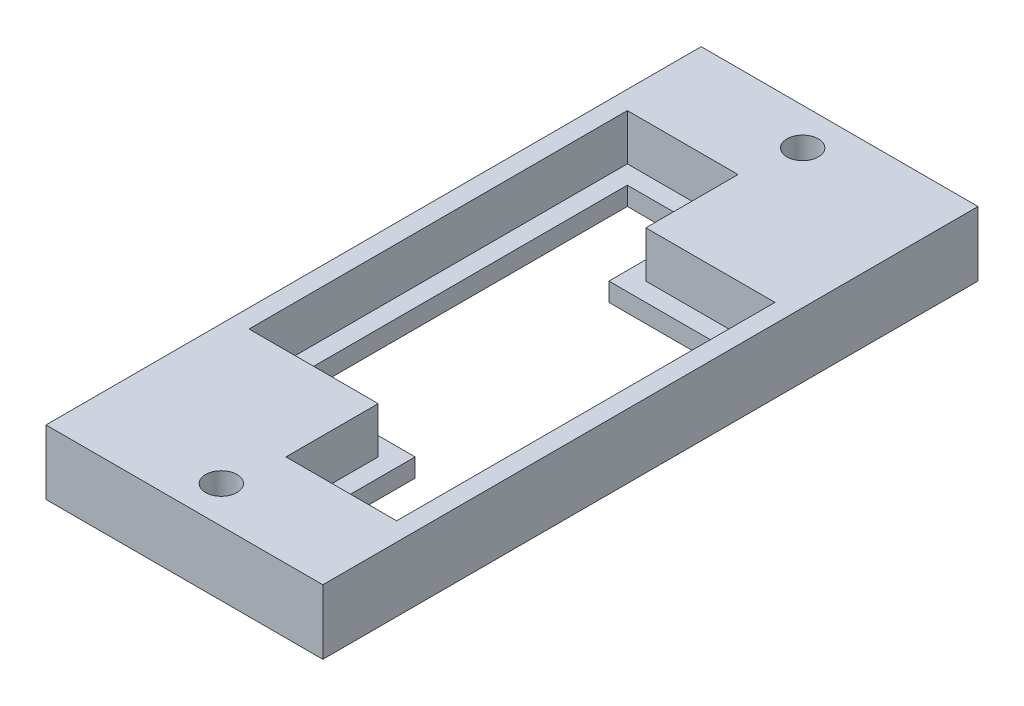
SolidWorks part; units mm, degrees
ref_plane "Front Plane" through (0, 0, 0) normal (0, 0, 1) x (1, 0, 0)
ref_plane "Top Plane" through (0, 0, 0) normal (0, 1, 0) x (1, 0, 0)
ref_plane "Right Plane" through (0, 0, 0) normal (1, 0, 0) x (0, 0, -1)
sketch "Sketch1" plane through (0, 0, 0) normal (0, 1, 0) x (1, 0, 0)
  line L0 (-16.022, 18.268) -> (-16.022, -22.732)
  line L1 (-16.022, -22.732) -> (-4.022, -22.732)
  line L2 (-4.022, -22.732) -> (-2.022, -22.732)
  line L3 (-2.022, -22.732) -> (-2.022, -32.732)
  line L4 (-2.022, -32.732) -> (9.978, -32.732)
  line L5 (9.978, -32.732) -> (9.978, 8.268)
  line L6 (9.978, 8.268) -> (-2.022, 8.268)
  line L7 (-2.022, 8.268) -> (-4.022, 8.268)
  line L8 (-4.022, 8.268) -> (-4.022, 18.268)
  line L9 (-4.022, 18.268) -> (-16.022, 18.268)
  line L10 (-6.022, 16.268) -> (-14.022, 16.268)
  line L11 (-14.022, 16.268) -> (-14.022, -20.732)
  line L12 (-14.022, -20.732) -> (-4.022, -20.732)
  line L13 (-4.022, -20.732) -> (-0.022, -20.732)
  line L14 (-0.022, -20.732) -> (-0.022, -30.732)
  line L15 (-0.022, -30.732) -> (7.978, -30.732)
  line L16 (7.978, -30.732) -> (7.978, 6.268)
  line L17 (7.978, 6.268) -> (-2.022, 6.268)
  line L18 (-2.022, 6.268) -> (-6.022, 6.268)
  line L19 (-6.022, 6.268) -> (-6.022, 16.268)
  line L20 (11.978, -34.732) -> (11.978, 10.268)
  line L21 (11.978, 10.268) -> (-2.022, 10.268)
  line L22 (-2.022, 10.268) -> (-2.022, 10.268)
  line L23 (-2.022, 10.268) -> (-2.022, 20.268)
  line L24 (-2.022, 20.268) -> (-18.022, 20.268)
  line L25 (-18.022, 20.268) -> (-18.022, -24.732)
  line L26 (-18.022, -24.732) -> (-4.022, -24.732)
  line L27 (-4.022, -24.732) -> (-4.022, -24.732)
  line L28 (-4.022, -24.732) -> (-4.022, -34.732)
  line L29 (-4.022, -34.732) -> (11.978, -34.732)
  line L30 (-18.022, 20.268) -> (-18.022, 28.268)
  line L31 (-18.022, 28.268) -> (11.978, 28.268)
  line L32 (11.978, 28.268) -> (11.978, 10.268)
  line L33 (-3.022, 28.268) -> (-3.022, -57.2701) construction
  line L34 (-18.022, 24.268) -> (11.978, 24.268) construction
  line L35 (-18.022, -24.732) -> (-18.022, -42.732)
  line L36 (-18.022, -42.732) -> (11.978, -42.732)
  line L37 (11.978, -42.732) -> (11.978, -34.732)
  line L38 (11.978, -38.732) -> (-18.022, -38.732) construction
  line L39 (11.978, 28.268) -> (11.978, 10.268)
  line L40 (11.978, 28.268) -> (11.978, 10.268)
  line L41 (-18.022, 28.268) -> (-18.022, 20.268)
  line L42 (-18.022, -42.732) -> (-18.022, -24.732)
  line L43 (11.978, -34.732) -> (11.978, -42.732)
  circle A0 centre (-3.022, 24.268) radius 1.7
  circle A1 centre (-3.022, -38.732) radius 1.7
  dimension "D8" = 8
  dimension "D1" = 41
  dimension "D2" = 12
  dimension "D3" = 2
  dimension "D4" = 41
  dimension "D5" = 10
  dimension "D9" = 30
  dimension "D10" = 18
  dimension "D11" = 18
  dimension "D12" = 8
  dimension "D6" = 2
  dimension "D7" = 2
extrude "Boss-Extrude1" add sketch "Sketch1" along normal blind 2 contours L8 L9 L0 L1 L2 L3 L4 L5 L6 L7 L19 L18 L17 L16 L15 L14 L13 L12 L11 L10 region at (-10.022, 0, -17.6955)
extrude "Boss-Extrude3" add sketch "Sketch1<5>" along normal blind 7 contours L28 L29 L20 L21 L23 L24 L25 L26 L9 L8 L7 L6 L5 L4 L3 L2 L1 L0 region at (3.978, 0, 34.1055)
sketch "Sketch1<5>" plane through (0, 0, 0) normal (0, 1, 0) x (1, 0, 0) same geometry as "Sketch1"
extrude "Boss-Extrude4" add sketch "Sketch1<6>" along normal blind 7 contours L36 L37 L29 L28 L26 L35 A1 | L32 L31 L30 L24 L23 L21 A0 region at (-6.0415, 0, 35.3351) region at (-0.0025, 0, -20.871)
sketch "Sketch1<6>" plane through (0, 0, 0) normal (0, 1, 0) x (1, 0, 0) same geometry as "Sketch1"
